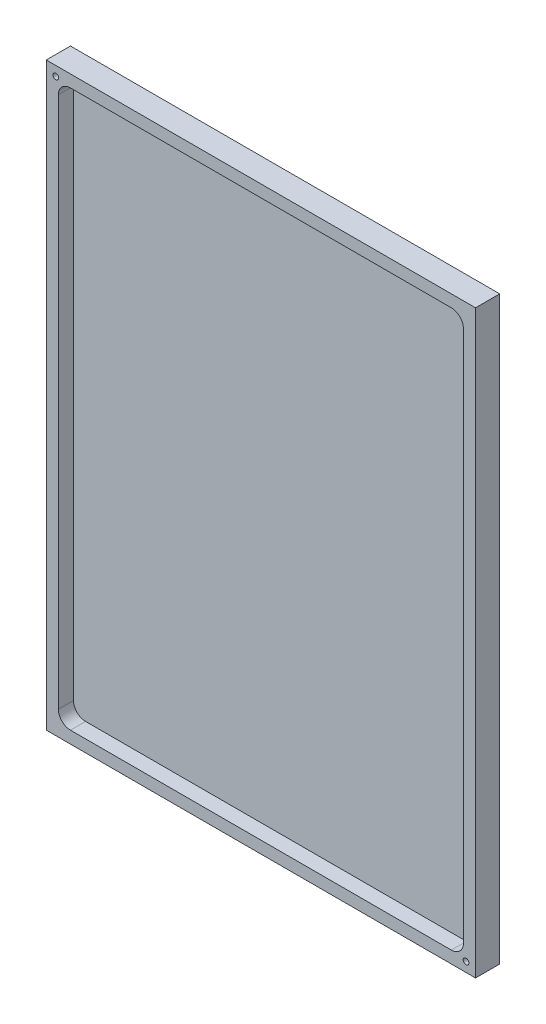
SolidWorks part; units mm, degrees
material "AISI 304"
ref_plane "Front Plane" through (0, 0, 0) normal (0, 0, 1) x (1, 0, 0)
ref_plane "Top Plane" through (0, 0, 0) normal (0, 1, 0) x (1, 0, 0)
ref_plane "Right Plane" through (0, 0, 0) normal (1, 0, 0) x (0, 0, -1)
sketch "Sketch1" plane through (0, 0, 0) normal (0, 0, 1) x (1, 0, 0)
  line L1 (112.7125, -152.4) -> (-112.7125, -152.4)
  line L2 (112.7125, -152.4) -> (112.7125, 152.4)
  line L3 (112.7125, 152.4) -> (-112.7125, 152.4)
  line L4 (-112.7125, -152.4) -> (-112.7125, 152.4)
  line L5 (112.7125, -152.4) -> (-112.7125, 152.4) construction
  line L6 (112.7125, 152.4) -> (-112.7125, -152.4) construction
  point P0 (0, 0)
  dimension "D1" = 304.8
  dimension "D2" = 225.425
extrude "Boss-Extrude1" add sketch "Sketch1" along normal blind 12.7
sketch "Sketch2" plane through (0, 0, 12.7) normal (0, 0, 1) x (1, 0, 0)
  line L0 (-112.7125, 152.4) -> (-112.7125, -152.4) construction
  line L1 (100.0125, -146.05) -> (-100.0125, -146.05)
  line L2 (106.3625, -139.7) -> (106.3625, 139.7)
  line L3 (100.0125, 146.05) -> (-100.0125, 146.05)
  line L4 (-106.3625, -139.7) -> (-106.3625, 139.7)
  line L5 (106.3625, -146.05) -> (-106.3625, 146.05) construction
  line L6 (106.3625, 146.05) -> (-106.3625, -146.05) construction
  line L7 (112.7125, 152.4) -> (-112.7125, 152.4) construction
  arc A0 (-100.0125, -146.05) -> (-106.3625, -139.7) centre (-100.0125, -139.7) cw
  arc A1 (100.0125, -146.05) -> (106.3625, -139.7) centre (100.0125, -139.7) ccw
  arc A2 (106.3625, 139.7) -> (100.0125, 146.05) centre (100.0125, 139.7) ccw
  arc A3 (-100.0125, 146.05) -> (-106.3625, 139.7) centre (-100.0125, 139.7) ccw
  point P0 (0, 0)
  dimension "D3" = 6.35
  dimension "D1" = 6.35
  dimension "D2" = 6.35
extrude "Cut-Extrude1" cut sketch "Sketch2" against normal blind 7.9375
sketch "Sketch3" [suppressed] plane through (0, 0, 12.7) normal (0, 0, 1) x (1, 0, 0)
  line L0 (105.1771, -142.2937) -> (106.8329, -144.7953) construction
  line L1 (104.2479, -146.5063) -> (102.5921, -144.0047) construction
  line L2 (105.1771, -142.2937) -> (106.8329, -144.7953) construction
  line L3 (104.2479, -146.5063) -> (102.5921, -144.0047) construction
  circle A0 centre (-104.7125, 144.4) radius 1.55 construction
  arc A1 (105.1771, -142.2937) -> (102.5921, -144.0047) centre (103.8846, -143.1492) ccw construction
  arc A2 (104.2479, -146.5063) -> (106.8329, -144.7953) centre (105.5404, -145.6508) ccw construction
  circle A3 centre (-104.7125, 144.4) radius 1.55 construction
  arc A4 (105.1771, -142.2937) -> (102.5921, -144.0047) centre (103.8846, -143.1492) ccw construction
  arc A5 (104.2479, -146.5063) -> (106.8329, -144.7953) centre (105.5404, -145.6508) ccw construction
hole_wizard "Ø3.0 (3) Diameter Hole1" positions "3DSketch1" profile "Sketch4" hole size "Ø3.0" standard "ANSI Metric"
sketch3d "3DSketch1"
  line L0 (-112.7125, -152.4, 12.7) -> (112.7125, -152.4, 12.7) construction
  line L1 (112.7125, -152.4, 12.7) -> (112.7125, 152.4, 12.7) construction
  line L2 (-112.7125, 152.4, 12.7) -> (-112.7125, -152.4, 12.7) construction
  line L3 (112.7125, 152.4, 12.7) -> (-112.7125, 152.4, 12.7) construction
  point P0 (-107.7125, 147.4, 12.7)
  point P2 (107.7125, -147.4, 12.7)
  dimension "D1" = 5
  dimension "D2" = 5
  dimension "D3" = 5
  dimension "D4" = 5
sketch "Sketch4" plane through (-107.7125, 147.4, 12.7) normal (1, 0, 0) x (0, -1, 0)
  line L0 (0, 0) -> (0, 5.9013)
  line L1 (0, 5.9013) -> (1.5, 5)
  line L2 (1.5, 5) -> (1.5, 0)
  line L5 (1.5, 0) -> (0, 0)
  line L10 (0, 5.9013) -> (-1.5, 5) construction
  line L11 (0, -6.35) -> (0, 107.95) construction
  dimension "Hole Dia." = 3
  dimension "Hole Depth" = 5
  dimension "Drill Angle" = 118
